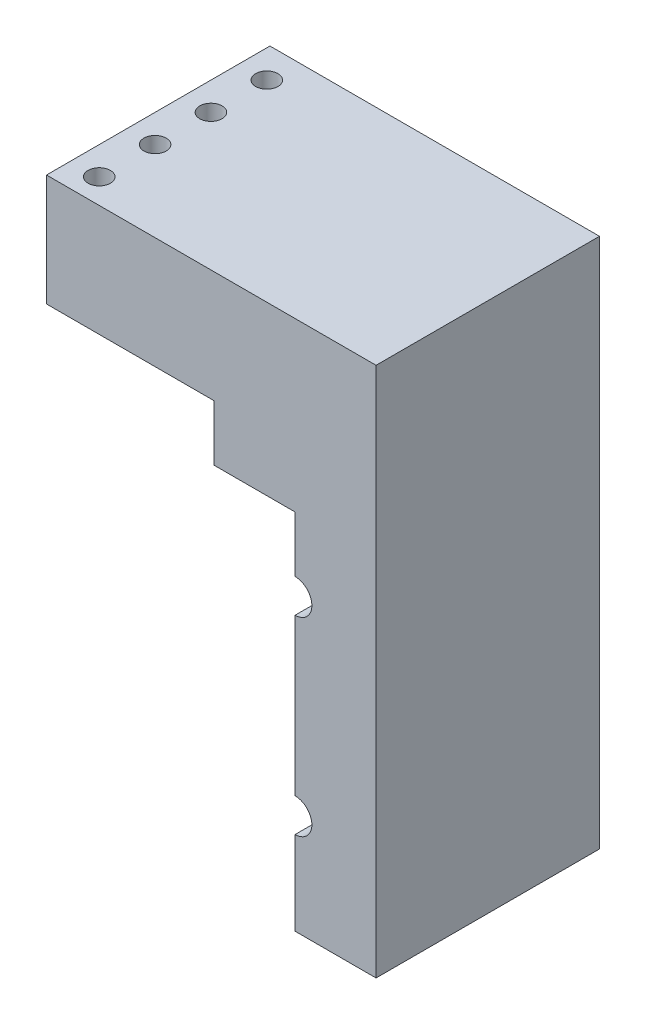
SolidWorks part; units mm, degrees
ref_plane "前视基准面" through (0, 0, 0) normal (0, 0, 1) x (1, 0, 0)
ref_plane "上视基准面" through (0, 0, 0) normal (0, 1, 0) x (1, 0, 0)
ref_plane "右视基准面" through (0, 0, 0) normal (1, 0, 0) x (0, 0, -1)
sketch "草图3" plane through (0, 0, 0) normal (0, 0, 1) x (1, 0, 0)
  line L1 (0, 0) -> (29, 0)
  line L2 (0, 0) -> (0, 95)
  line L3 (0, 95) -> (29, 95)
  line L4 (29, 0) -> (29, 95)
extrude "凸台-拉伸1" add sketch "草图3" along normal blind 40
sketch "草图4" plane through (0, 0, 40) normal (0, 0, 1) x (1, 0, 0)
  line L0 (0, 0) -> (29, 0) construction
  circle A2 centre (14.5, 52) radius 3.005
  circle A3 centre (14.5, 18) radius 3.005
  circle A4 centre (14.5, 52) radius 3.025
  circle A5 centre (14.5, 18) radius 3.025
  dimension "D1" = 34
  dimension "D2" = 18
  dimension "D3" = 0.02
  dimension "D4" = 0.02
extrude "切除-拉伸1" cut sketch "草图4" against normal through all contours A2 | A3
sketch "草图6" plane through (0, 0, 0) normal (-1, 0, 0) x (0, 0, 1)
  line L0 (40, 95) -> (40, 0) construction
  line L1 (0, 95) -> (40, 95)
  line L2 (0, 95) -> (0, 75)
  line L3 (0, 75) -> (40, 75)
  line L4 (40, 95) -> (40, 75)
extrude "凸台-拉伸3" add sketch "草图6" along normal blind 30
sketch "草图7" plane through (0, 0, 40) normal (0, 0, 1) x (1, 0, 0)
  line L0 (0, 75) -> (0, 0) construction
  line L1 (0, 65) -> (14.5, 65)
  line L2 (0, 65) -> (0, 0)
  line L3 (0, 0) -> (14.5, 0)
  line L4 (14.5, 65) -> (14.5, 0)
  line L5 (0, 0) -> (29, 0) construction
extrude "切除-拉伸2" cut sketch "草图7" against normal through all
sketch "草图9" plane through (14.5, 0, 0) normal (-1, 0, 0) x (0, 0, 1)
  line L0 (0, 55.005) -> (0, 65) construction
  circle A0 centre (5, 60.0025) radius 2
  circle A1 centre (15, 60.0025) radius 2
  circle A2 centre (25, 60.0025) radius 2
  circle A3 centre (35, 60.0025) radius 2
  dimension "D1" = 4
  dimension "D2" = 5
  dimension "D3" = 10
  dimension "D4" = 10
  dimension "D5" = 10
extrude "切除-拉伸4" cut sketch "草图9" against normal blind 5
sketch "草图10" plane through (14.5, 0, 0) normal (-1, 0, 0) x (0, 0, 1)
  line L0 (0, 0) -> (0, 14.995) construction
  circle A0 centre (5, 7.4975) radius 2
  circle A1 centre (15, 7.4975) radius 2
  circle A2 centre (25, 7.4975) radius 2
  circle A3 centre (35, 7.4975) radius 2
  dimension "D1" = 4
  dimension "D2" = 5
  dimension "D3" = 10
  dimension "D4" = 10
  dimension "D5" = 10
extrude "切除-拉伸5" cut sketch "草图10" against normal blind 5
sketch "草图11" plane through (14.5, 0, 0) normal (-1, 0, 0) x (0, 0, 1)
  line L0 (0, 21.005) -> (0, 48.995) construction
  circle A0 centre (5, 35) radius 2
  circle A1 centre (15, 35) radius 2
  circle A2 centre (25, 35) radius 2
  circle A3 centre (35, 35) radius 2
  dimension "D1" = 4
  dimension "D2" = 10
  dimension "D3" = 5
  dimension "D4" = 10
  dimension "D5" = 10
extrude "切除-拉伸6" cut sketch "草图11" against normal blind 5
sketch "草图12" plane through (0, 95, 0) normal (0, 1, 0) x (1, 0, 0)
  line L0 (-30, -40) -> (-30, 0) construction
  circle A0 centre (-25, -35.5635) radius 2
  circle A1 centre (-25, -25.5635) radius 2
  circle A2 centre (-25, -15.5635) radius 2
  circle A3 centre (-25, -5.5635) radius 2
  point P10 (0, 0)
  point P11 (0, 0)
  dimension "D1" = 4
  dimension "D3" = 10
  dimension "D2" = 10
  dimension "D4" = 10
  dimension "D5" = 5
extrude "切除-拉伸7" cut sketch "草图12" against normal blind 5
